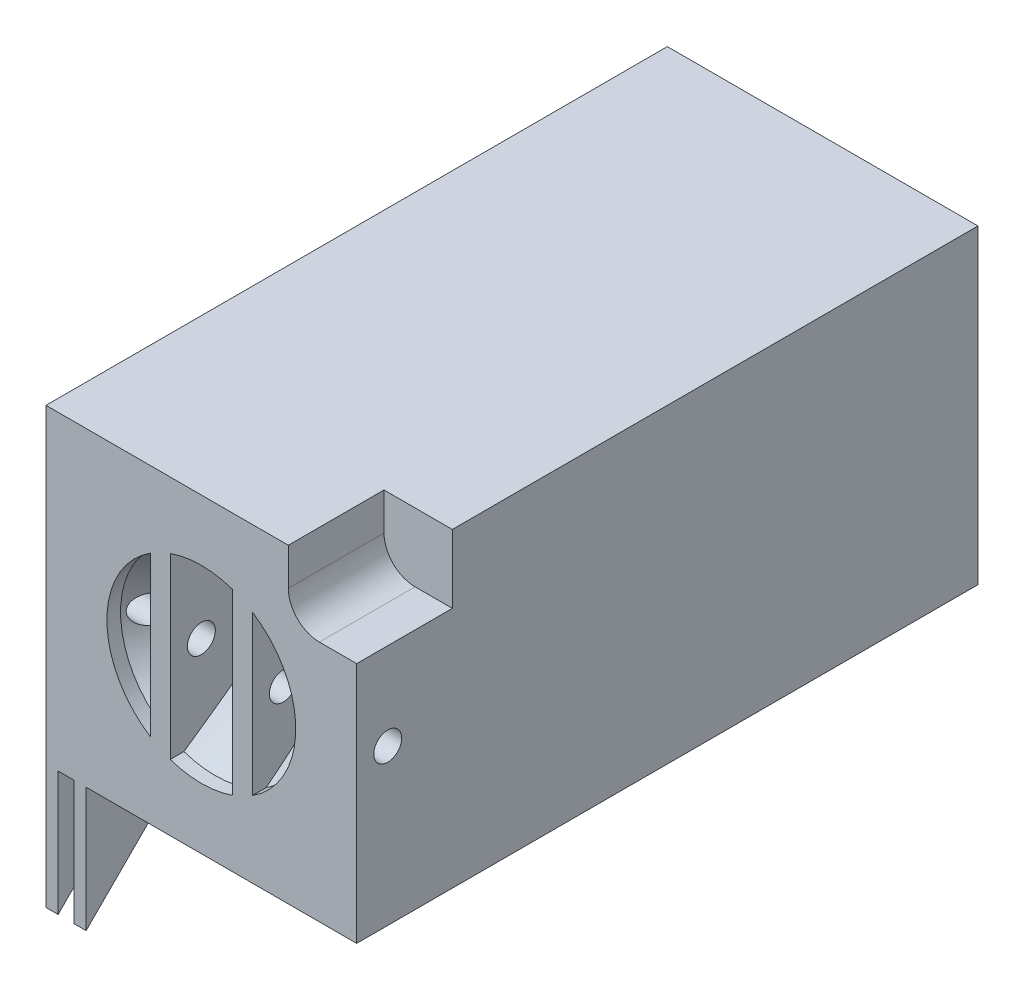
SolidWorks part; units mm, degrees
ref_plane "Alzado" through (0, 0, 0) normal (0, 0, 1) x (1, 0, 0)
ref_plane "Planta" through (0, 0, 0) normal (0, 1, 0) x (1, 0, 0)
ref_plane "Vista lateral" through (0, 0, 0) normal (1, 0, 0) x (0, 0, -1)
sketch "Croquis1" plane through (0, 0, 0) normal (0, 0, 1) x (1, 0, 0)
  line L1 (25, -25) -> (-25, -25)
  line L2 (25, -25) -> (25, 25)
  line L3 (25, 25) -> (-25, 25)
  line L4 (-25, -25) -> (-25, 25)
  line L5 (25, -25) -> (-25, 25) construction
  line L6 (25, 25) -> (-25, -25) construction
  circle A0 centre (0, 0) radius 2
  point P0 (0, 0)
  dimension "D3" = 4
  dimension "D1" = 50
  dimension "D2" = 50
extrude "Saliente-Extruir2" add sketch "Croquis1" along normal blind 100
ref_plane "Plano1" through (0, 0, 0) normal (1, 0, 0) x (0, 0, -1)
sketch "Croquis2" plane through (0, 0, 0) normal (1, 0, 0) x (0, 0, -1)
  line L1 (-100, 25) -> (-100, -25) construction
  line L4 (-100, 15.2) -> (-100, 0)
  line L6 (-97.8, 15.2) -> (-89.8, 10)
  line L7 (-100, 15.2) -> (-97.8, 15.2)
  line L8 (-89.8, 0) -> (-89.8, 10)
  line L9 (-100, 0) -> (-89.8, 0)
  dimension "D1" = 2.2
  dimension "D2" = 10.2
  dimension "D3" = 10
  dimension "D4" = 15.2
revolve "Cortar-Revolución1" cut sketch "Croquis2" angle 360 about L9
sketch "Croquis4" plane through (0, 0, 100) normal (0, 0, 1) x (1, 0, 0)
  line L0 (0, -0.44) -> (0, 0.44) construction
  line L1 (-8.2, 20) -> (-5, 20)
  line L2 (-8.2, 20) -> (-8.2, -20)
  line L3 (-8.2, -20) -> (-5, -20)
  line L4 (-5, 20) -> (-5, -20)
  line L5 (8.2, -20) -> (5, -20)
  line L6 (5, 20) -> (5, -20)
  line L7 (8.2, 20) -> (5, 20)
  line L8 (8.2, 20) -> (8.2, -20)
  point P6 (-5, 0)
  dimension "D1" = 3.2
  dimension "D2" = 5
  dimension "D3" = 40
extrude "Saliente-Extruir5" add sketch "Croquis4" along direction (0, 0, 1) on the side against the normal up to surface (10.2 mm away) up to face at (0, -2, 89.8)
sketch "Croquis8" plane through (0, 0, 89.8) normal (0, 0, 1) x (1, 0, 0)
  circle A0 centre (0, 0) radius 4
  dimension "D1" = 8
extrude "Cortar-Extruir3" cut sketch "Croquis8" against normal offset from surface (87.4 mm away) 2.4 up to face at (0, 0, 0)
sketch "Croquis7" plane through (-25, 0, 0) normal (-1, 0, 0) x (0, 0, 1)
  line L1 (100, 25) -> (100, -25) construction
  circle A0 centre (95, 0) radius 2
  dimension "D1" = 4
  dimension "D2" = 5
extrude "Cortar-Extruir2" cut sketch "Croquis7" against normal up to vertex (50 mm away) up to point (25, -25, 100)
hole_wizard "Refrentado para tornillo tapón con cabeza plana de clavija de M41" positions "Croquis10" profile "Croquis11" countersink size "M4" standard "Ansi Metric" end condition through all
sketch "Croquis10" plane through (-25, 0, 0) normal (-1, 0, 0) x (0, 0, 1)
  point P0 (95, 0)
sketch "Croquis11" plane through (-25, 0, 95) normal (0, 1, 0) x (0, 0, 1)
  line L0 (0, 0) -> (0, 50)
  line L1 (0, 50) -> (2.25, 50)
  line L2 (2.25, 50) -> (2.25, 2.23)
  line L3 (2.25, 2.23) -> (4.48, 0)
  line L5 (4.48, 0) -> (0, 0)
  line L6 (-2.25, 2.23) -> (-4.48, 0) construction
  line L11 (0, -6.35) -> (0, 107.95) construction
  dimension "Diámetro de taladro hasta el siguiente" = 4.5
  dimension "Profundidad de taladro hasta el siguiente" = 50
  dimension "Diámetro de avellanado cercano" = 8.96
  dimension "Ángulo de avellanado cercano" = 90
sketch "Croquis12" plane through (-25, 0, 0) normal (-1, 0, 0) x (0, 0, 1)
  line L1 (100, -25) -> (80, -25)
  line L2 (100, 0) -> (0, 0) construction
  line L5 (100, 25) -> (100, -25) construction
  line L6 (0, 25) -> (0, -25) construction
  line L10 (100, -25) -> (100, -45)
  line L11 (100, -45) -> (80, -25)
extrude "Saliente-Extruir6" add sketch "Croquis12" against normal blind 1.95
extrude "Saliente-Extruir7" add sketch "Croquis12<2>" against normal blind 1.95 from offset 4.5 offset against normal yes
sketch "Croquis12<2>" plane through (-25, 0, 0) normal (-1, 0, 0) x (0, 0, 1) same geometry as "Croquis12"
sketch "Croquis13" plane through (0, 0, 100) normal (0, 0, 1) x (1, 0, 0)
  line L0 (25, 25) -> (25, 14)
  line L1 (25, -25) -> (25, 25) construction
  line L2 (25, 14) -> (19, 14)
  line L3 (14, 19) -> (14, 25)
  line L4 (25, 25) -> (-25, 25) construction
  line L5 (14, 25) -> (25, 25)
  line L6 (25, 25) -> (19.8028, 19.8028) construction
  arc A0 (19, 14) -> (14, 19) centre (19, 19) cw
  dimension "D3" = 5
  dimension "D1" = 11
  dimension "D2" = 11
  dimension "D4" = 45
  dimension "D5" = 7.35
extrude "Cortar-Extruir4" cut sketch "Croquis13" against normal blind 15.4
